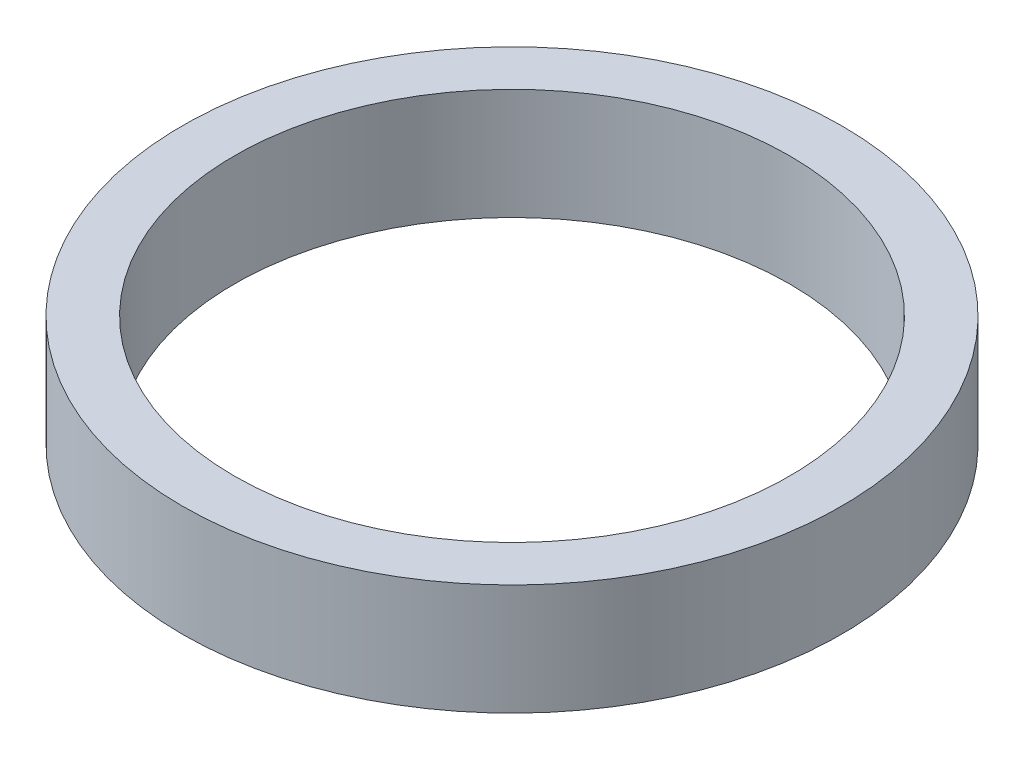
SolidWorks part; units mm, degrees
ref_plane "Front Plane" through (0, 0, 0) normal (0, 0, 1) x (1, 0, 0)
ref_plane "Top Plane" through (0, 0, 0) normal (0, 1, 0) x (1, 0, 0)
ref_plane "Right Plane" through (0, 0, 0) normal (1, 0, 0) x (0, 0, -1)
sketch "Sketch1" plane through (0, 0, 0) normal (0, 1, 0) x (1, 0, 0)
  circle A0 centre (0, 0) radius 47.5
  dimension "FLANGE_OD" = 95
extrude "Boss-Extrude1" add sketch "Sketch1" along normal blind 16
sketch "Sketch2" plane through (0, 0, 0) normal (0, 1, 0) x (1, 0, 0)
  circle A0 centre (0, 0) radius 40
  dimension "BORE_D" = 80
extrude "Cut-Extrude1" cut sketch "Sketch2" along normal through all
sketch "Sketch3" plane through (0, 16, 0) normal (0, 1, 0) x (1, 0, 0)
  circle A0 centre (0, 0) radius 21.4697 construction
  circle A1 centre (-21.4697, 0) radius 1.5
  dimension "BOLT_D" = 3
  dimension "BOLT_PCD" = 42.9394
extrude "Cut-Extrude2" cut sketch "Sketch3" against normal blind 10.5 rebuild error yes
pattern_circular "CirPattern1" count 4 over 360 rebuild error yes
